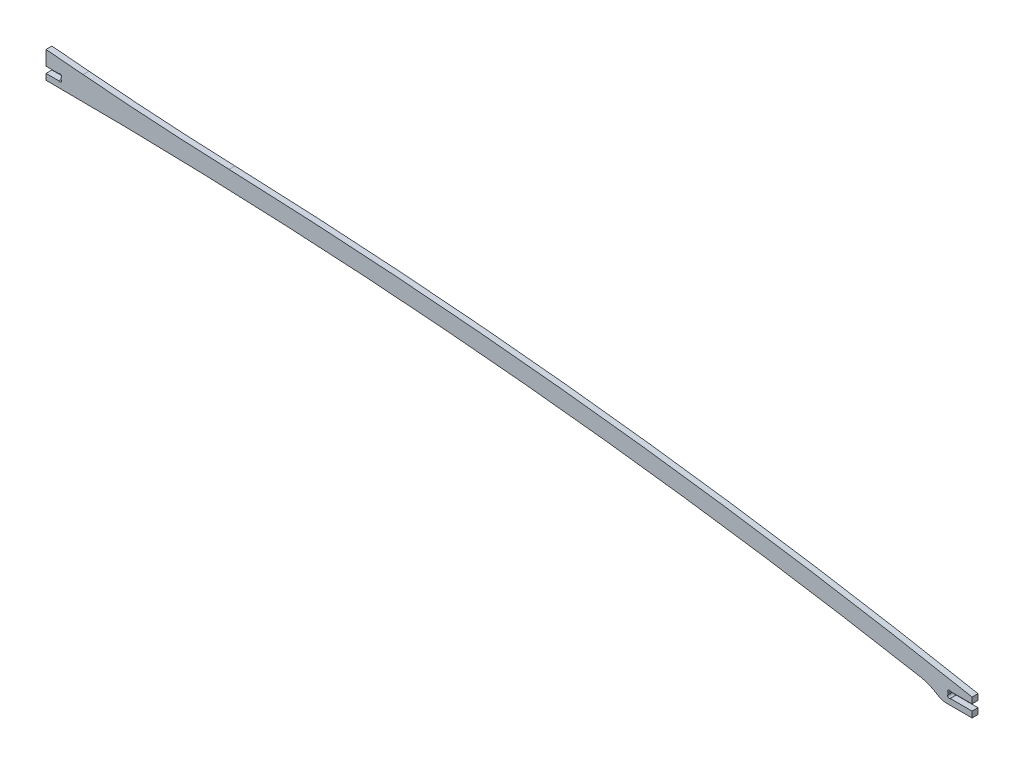
SolidWorks part; units mm, degrees
material "自定义塑料碳纤维-1.6"
ref_plane "前视基准面" through (0, 0, 0) normal (0, 0, 1) x (1, 0, 0)
ref_plane "上视基准面" through (0, 0, 0) normal (0, 1, 0) x (1, 0, 0)
ref_plane "右视基准面" through (0, 0, 0) normal (1, 0, 0) x (0, 0, -1)
other "Configuration Table"
sketch "草图1" plane through (0, 0, 0) normal (0, 0, 1) x (1, 0, 0)
  line L0 (-1642.6042, 0) -> (1642.6042, 0)
  line L1 (312.5, 1612.6042) -> (-312.5, 1612.6042)
  line L2 (0, 1642.6042) -> (312.5, 1642.6042)
  line L3 (312.5, 1642.6042) -> (312.5, 1612.6042)
  line L4 (312.5, 1612.6042) -> (312.5, 1606.4921)
  line L5 (312.5, 1606.4921) -> (-342.5369, 1606.4921)
  line L6 (-312.5, 1612.6042) -> (-312.5, 1606.4921)
  line L7 (0, 1642.6042) -> (0, 1636.6042)
  circle A0 centre (0, 0) radius 1642.6042
  circle A1 centre (0, 0) radius 1636.6042
  dimension "D1" = 30
  dimension "D2" = 6
  dimension "D3" = 625
extrude "凸台-拉伸1" add sketch "草图1" along normal mid plane 2 contours A1 L1 A0 L7 | A1 L4 L1 region at (301.5262, 1610.5863, 0) region at (148.6564, 1630.632, 0)
sketch "草图2" plane through (0, 0, 1) normal (0, 0, 1) x (1, 0, 0)
  line L0 (312.5, 1609.5481) -> (304.4, 1609.5481)
  line L1 (312.5, 1612.6042) -> (312.5, 1606.4921) construction
  line L2 (304.4, 1609.5481) -> (304.4, 1610.5981)
  line L3 (304.4, 1610.5981) -> (312.5, 1610.5981)
  line L4 (312.5, 1610.5981) -> (312.5, 1608.4981)
  line L5 (312.5, 1608.4981) -> (304.4, 1608.4981)
  line L6 (304.4, 1608.4981) -> (304.4, 1609.5481)
  line L7 (312.5, 1606.4921) -> (302.5, 1606.4921)
  line L8 (302.5, 1606.4921) -> (297.6056, 1609.3179)
  line L9 (297.6056, 1609.3179) -> (304.4, 1610.5981)
  line L10 (312.5, 1608.4981) -> (312.5, 1606.4921)
  arc A0 (312.5, 1606.4921) -> (0, 1636.6042) centre (0, 0) ccw construction
  arc M5 (0, 1636.6042) -> (312.5, 1606.4921) centre (0, 0) cw
  line M6 (312.5, 1606.4921) -> (312.5, 1612.6042)
  dimension "D1" = 2.1
  dimension "D2" = 8.1
  dimension "D3" = 150
  dimension "D4" = 10
extrude "凸台-拉伸2" add sketch "草图2" against normal up to surface (2 mm away) contours L9 L5 L6 L2 M5 M6 | L8 L7 M5 region at (304.2455, 1609.0231, 1) region at (304.2124, 1607.44, 1) up to face at (156.6105, 1628.3245, -1)
extrude "切除-拉伸1" cut sketch "草图2<3>" against normal through all contours L3 L2 L0 M6 | L6 L5 L0 M6 region at (308.45, 1609.0231, 1) region at (308.45, 1610.0731, 1)
sketch "草图2<3>" plane through (0, 0, 1) normal (0, 0, 1) x (1, 0, 0) same geometry as "草图2"
sketch "草图3" plane through (0, 0, 1) normal (0, 0, 1) x (1, 0, 0)
  line L0 (0, 1642.6042) -> (0, 1645.6042)
  line L1 (0, -55) -> (0, 55) construction
  line L2 (0, 1645.6042) -> (40, 1642.1171)
  arc A0 (312.5, 1612.6042) -> (0, 1642.6042) centre (0, 0) ccw construction
  arc M6 (312.5, 1612.6042) -> (0, 1642.6042) centre (0, 0) ccw
  dimension "D1" = 3
  dimension "D2" = 40
extrude "凸台-拉伸3" add sketch "草图3" against normal up to surface (2 mm away) contours L2 L0 M6 region at (12.9518, 1643.5009, 1) up to face at (246.0248, 1616.6597, -1)
fillet "圆角1" radius 1000 1 edges at (40, 1642.1171, 0)
sketch "草图4" plane through (0, 0, 1) normal (0, 0, 1) x (1, 0, 0)
  line L0 (0, 1638.6042) -> (5.1, 1638.6042)
  line L1 (0, -1.1) -> (0, 1.1) construction
  line L2 (5.1, 1638.6042) -> (5.1, 1640.7042)
  line L3 (5.1, 1640.7042) -> (0, 1640.7042)
  line L4 (0, 1640.7042) -> (0, 1638.6042)
  dimension "D3" = 2
  dimension "D1" = 5.1
  dimension "D2" = 2.1
extrude "切除-拉伸2" cut sketch "草图4" against normal through all
sketch "草图5" plane through (0, 0, 1) normal (0, 0, 1) x (1, 0, 0)
  line L0 (4.7464, 1640.3506) -> (5.1, 1640.7042)
  line L1 (4.7464, 1638.9577) -> (5.1, 1638.6042)
  line L2 (5.1, 1638.6042) -> (5.1, 1640.7042) construction
  line L3 (0, 1638.6042) -> (5.1, 1638.6042) construction
  line L4 (304.7536, 1610.2446) -> (304.4, 1610.5981)
  line L5 (304.7536, 1608.8517) -> (304.4, 1608.4981)
  line L6 (304.4, 1610.5981) -> (312.5, 1610.5981) construction
  line L7 (304.4, 1608.4981) -> (304.4, 1610.5981) construction
  circle A0 centre (304.7536, 1610.2446) radius 0.5
  circle A1 centre (304.7536, 1608.8517) radius 0.5
  circle A2 centre (4.7464, 1640.3506) radius 0.5
  circle A3 centre (4.7464, 1638.9577) radius 0.5
  line M5 (0, 1640.7042) -> (5.1, 1640.7042)
  line M6 (5.1, 1640.7042) -> (5.1, 1638.6042)
  line M7 (5.1, 1638.6042) -> (0, 1638.6042)
  line M13 (312.5, 1608.4981) -> (304.4, 1608.4981)
  line M14 (304.4, 1608.4981) -> (304.4, 1610.5981)
  line M15 (304.4, 1610.5981) -> (312.5, 1610.5981)
  dimension "D1" = 1
  dimension "D2" = 45
  dimension "D3" = 45
  dimension "D4" = 45
  dimension "D5" = 45
extrude "切除-拉伸3" cut sketch "草图5" against normal blind 10 contours A1 M14 | A1 M13 | A0 M14 | A0 M15 | A2 M6 | A2 M5 | A3 M6 | A3 M7 region at (304.3406, 1608.8517, 1) region at (304.7536, 1610.6575, 1) region at (304.3406, 1610.2446, 1) region at (304.7536, 1608.4388, 1) region at (5.1594, 1640.3506, 1) region at (5.1594, 1638.9577, 1) region at (4.7464, 1640.7635, 1) region at (4.7464, 1638.5448, 1)
fillet "圆角2" radius 0.3 8 edges at (5.1, 1639.9971, 0) (4.3929, 1640.7042, 0) (304.4, 1609.891, 0) (305.1071, 1608.4981, 0) (304.4, 1609.2053, 0) (305.1071, 1610.5981, 0) (4.3929, 1638.6042, 0) (5.1, 1639.3113, 0)
fillet "圆角3" radius 15 1 edges at (297.6056, 1609.3179, 0)
fillet "圆角4" radius 5 1 edges at (302.5, 1606.4921, 0)
